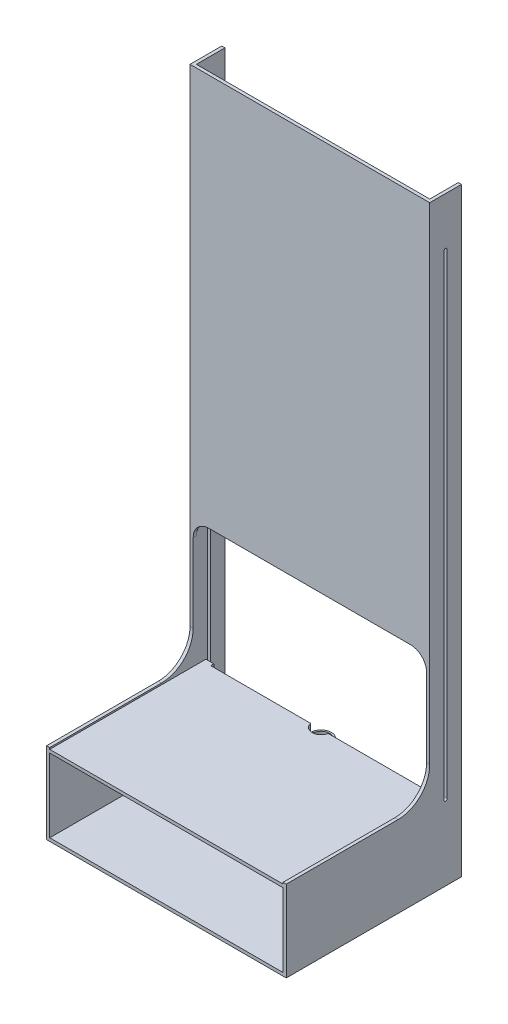
SolidWorks part; units mm, degrees
material "AISI 4340 Steel, annealed"
ref_plane "Front Plane" through (0, 0, 0) normal (0, 0, 1) x (1, 0, 0)
ref_plane "Top Plane" through (0, 0, 0) normal (0, 1, 0) x (1, 0, 0)
ref_plane "Right Plane" through (0, 0, 0) normal (1, 0, 0) x (0, 0, -1)
ref_plane "Right side of elevator platform" through (368, 0, 0) normal (1, 0, 0) x (0, 0, -1)
sketch "Sketch2" plane through (368, 0, 0) normal (1, 0, 0) x (0, 0, -1)
  line L0 (50, 236.5) -> (50, 1736.5) construction
  line L1 (45, 236.5) -> (45, 1736.5)
  line L2 (55, 236.5) -> (55, 1736.5)
  line L4 (0, 0) -> (100, 0)
  line L5 (0, 0) -> (0, 1800)
  line L6 (0, 1800) -> (100, 1800)
  line L7 (100, 0) -> (100, 1800)
  arc A0 (45, 236.5) -> (55, 236.5) centre (50, 236.5) ccw
  arc A1 (55, 1736.5) -> (45, 1736.5) centre (50, 1736.5) ccw
  point P2 (50, 986.5)
  dimension "D6" = 5
  dimension "D1" = 1800
  dimension "D2" = 100
  dimension "D3" = 50
  dimension "D4" = 236.5
  dimension "D5" = 63.5
extrude "Right side guide" add sketch "Sketch2" along normal blind 10
sketch "Sketch3" plane through (368, 0, 0) normal (-1, 0, 0) x (0, 0, 1)
  line L0 (0, 1800) -> (0, 0) construction
  line L1 (-100, 0) -> (0, 0)
  line L2 (-100, 0) -> (-100, 10)
  line L3 (-100, 10) -> (0, 10)
  line L4 (0, 0) -> (0, 10)
  dimension "D1" = 10
extrude "Bottom connection" add sketch "Sketch3" along normal blind 736
sketch "Sketch4" plane through (-368, 0, 0) normal (-1, 0, 0) x (0, 0, 1)
  line L0 (-55, 236.5) -> (-55, 1736.5) construction
  line L1 (-45, 1736.5) -> (-45, 236.5) construction
  line L2 (-55, 236.5) -> (-55, 1736.5)
  line L3 (-45, 1736.5) -> (-45, 236.5)
  line L4 (-100, 10) -> (0, 10)
  line L5 (0, 10) -> (0, 1800)
  line L6 (0, 1800) -> (-100, 1800)
  line L7 (-100, 1800) -> (-100, 10)
  line L9 (0, 10) -> (0, 1800)
  line L10 (0, 1800) -> (-100, 1800)
  line L11 (-100, 1800) -> (-100, 10)
  line L16 (-100, 10) -> (-100, 0)
  line L17 (-100, 0) -> (0, 0)
  line L18 (0, 0) -> (0, 10)
  line L19 (0, 10) -> (-100, 10)
  line L20 (-100, 10) -> (-100, 0)
  line L21 (-100, 0) -> (0, 0)
  line L22 (0, 0) -> (0, 10)
  arc A0 (-45, 1736.5) -> (-55, 1736.5) centre (-50, 1736.5) ccw construction
  arc A1 (-55, 236.5) -> (-45, 236.5) centre (-50, 236.5) ccw construction
  arc A2 (-45, 1736.5) -> (-55, 1736.5) centre (-50, 1736.5) ccw
  arc A3 (-55, 236.5) -> (-45, 236.5) centre (-50, 236.5) ccw
  dimension "D1" = 0
  dimension "D2" = 0
extrude "Left side guide" add sketch "Sketch4" along normal blind 10
sketch "Sketch5" plane through (0, 0, 0) normal (0, 0, 1) x (1, 0, 0)
  line L0 (-368, 10) -> (-368, 1800) construction
  line L1 (-368, 1800) -> (368, 1800)
  line L2 (-368, 1800) -> (-368, 653.8)
  line L3 (-368, 653.8) -> (368, 653.8)
  line L4 (368, 1800) -> (368, 653.8)
  line L5 (368, 1800) -> (368, 10) construction
  line L6 (378, 1800) -> (368, 1800) construction
  line L7 (-368, 10) -> (368, 10) construction
  dimension "D1" = 643.8
extrude "Structural webbing extrude" add sketch "Sketch5" against normal blind 10
sketch "Sketch6" plane through (0, 0, 0) normal (0, 0, 1) x (1, 0, 0)
  line L0 (-378, 251.5) -> (-378, 0)
  line L1 (-378, 0) -> (-378, 1800) construction
  line L2 (-378, 0) -> (378, 0)
  line L3 (378, 0) -> (378, 251.5)
  line L4 (378, 1800) -> (378, 0) construction
  line L5 (378, 251.5) -> (368, 251.5)
  line L6 (368, 653.8) -> (368, 10) construction
  line L7 (368, 251.5) -> (368, 10)
  line L8 (368, 10) -> (-368, 10)
  line L9 (-368, 10) -> (-368, 251.5)
  line L10 (-368, 10) -> (-368, 653.8) construction
  line L11 (-368, 251.5) -> (-378, 251.5)
  dimension "D1" = 241.5
extrude "Input roller holder extrude" add sketch "Sketch6" along normal blind 452.52
sketch "Sketch7" plane through (368, 0, 0) normal (-1, 0, 0) x (0, 0, 1)
  line L0 (0, 653.8) -> (0, 251.5) construction
  line L1 (452.52, 251.5) -> (-40, 251.5)
  line L2 (452.52, 251.5) -> (452.52, 241.5)
  line L3 (452.52, 241.5) -> (-40, 241.5)
  line L4 (-40, 251.5) -> (-40, 241.5)
  dimension "D1" = 40
  dimension "D2" = 10
extrude "Input roller platform" add sketch "Sketch7" along normal up to next
sketch "Sketch8" plane through (0, 251.5, 0) normal (0, 1, 0) x (1, 0, 0)
  line L1 (-378, -452.52) -> (-368, -452.52)
  line L2 (-378, -452.52) -> (-378, 0)
  line L3 (-378, 0) -> (-368, 0)
  line L4 (-368, -452.52) -> (-368, 0)
  line L5 (368, 0) -> (378, 0)
  line L6 (368, 0) -> (368, -452.52)
  line L7 (368, -452.52) -> (378, -452.52)
  line L8 (378, 0) -> (378, -452.52)
extrude "Siding outline" add sketch "Sketch8" along normal blind 5
sketch "Sketch9" plane through (0, 1800, 0) normal (0, 1, 0) x (1, 0, 0)
  line L8 (368, 100) -> (368, 10)
  line L9 (368, 10) -> (-368, 10)
  line L10 (-368, 10) -> (-368, 100)
  line L11 (-368, 100) -> (-378, 100)
  line L12 (-378, 100) -> (-378, 0)
  line L13 (-378, 0) -> (378, 0)
  line L14 (378, 0) -> (378, 100)
  line L15 (378, 100) -> (368, 100)
  line L16 (368, 100) -> (368, 10)
  line L17 (368, 10) -> (-368, 10)
  line L18 (-368, 10) -> (-368, 100)
  line L19 (-368, 100) -> (-378, 100)
  line L20 (-378, 100) -> (-378, 0)
  line L21 (-378, 0) -> (378, 0)
  line L22 (378, 0) -> (378, 100)
  line L23 (378, 100) -> (368, 100)
  dimension "D1" = 0
extrude "Lip to prevent box from falling out" add sketch "Sketch9" along normal blind 91.5
fillet "Vertical section fillets" radius 100 2 edges at (373, 256.5, 0) (-373, 256.5, 0)
fillet "Smaller fillets" radius 50 2 edges at (368, 653.8, -5) (-368, 653.8, -5)
sketch "Sketch11" plane through (0, 0, -40) normal (0, 0, -1) x (-1, 0, 0)
  line L0 (368, 251.5) -> (-368, 251.5) construction
  line L1 (-343, 251.5) -> (343, 251.5)
  line L2 (-343, 251.5) -> (-343, 241.5)
  line L3 (-343, 241.5) -> (343, 241.5)
  line L4 (343, 251.5) -> (343, 241.5)
  line L5 (368, 241.5) -> (-368, 241.5) construction
  line L6 (-368, 251.5) -> (-368, 241.5) construction
  line L7 (368, 251.5) -> (368, 241.5) construction
  dimension "D1" = 25
  dimension "D2" = 25
extrude "Gate spacing cut" cut sketch "Sketch11" against normal blind 10
sketch "Sketch12" plane through (-368, 0, 0) normal (1, 0, 0) x (0, 0, -1)
  line L1 (45, 221.5) -> (40, 221.5)
  line L2 (45, 221.5) -> (45, 10)
  line L3 (45, 10) -> (40, 10)
  line L4 (40, 221.5) -> (40, 10)
  line L5 (100, 1891.5) -> (100, 10) construction
  line L6 (45, 236.5) -> (45, 1736.5) construction
  line L7 (-452.52, 10) -> (100, 10) construction
  line L8 (40, 241.5) -> (-452.52, 241.5) construction
  line L9 (30, 241.5) -> (25, 241.5)
  line L10 (30, 241.5) -> (30, 10)
  line L11 (30, 10) -> (25, 10)
  line L12 (25, 241.5) -> (25, 10)
  dimension "D1" = 60
  dimension "D2" = 20
  dimension "D3" = 5
extrude "Gate guide rails" add sketch "Sketch12" along normal up to next
sketch "Sketch13" plane through (0, 0, -45) normal (0, 0, -1) x (-1, 0, 0)
  line L0 (-368, 221.5) -> (368, 221.5) construction
  line L1 (-328, 221.5) -> (328, 221.5)
  line L2 (-328, 221.5) -> (-328, 10)
  line L3 (-328, 10) -> (328, 10)
  line L4 (328, 221.5) -> (328, 10)
  line L5 (368, 10) -> (-368, 10) construction
  line L6 (-368, 10) -> (-368, 1891.5) construction
  point P8 (0, 221.5)
  dimension "D1" = 40
extrude "Gate rod connection cutout" cut sketch "Sketch13" against normal through all
sketch "Sketch14" plane through (0, 10, 0) normal (0, 1, 0) x (1, 0, 0)
  line L0 (328, 45) -> (-328, 25) construction
  circle A0 centre (0, 35) radius 28
  circle A1 centre (0, 35) radius 33
  point P7 (0, 35)
  dimension "D1" = 56
  dimension "D2" = 5
extrude "Spring cup" add sketch "Sketch14" along normal blind 75
sketch "Sketch15" plane through (0, 85, 0) normal (0, 1, 0) x (1, 0, 0)
  line L0 (368, 30) -> (328, 30) construction
  line L1 (32.619, 30) -> (27.55, 30)
  line L3 (32.619, 40) -> (27.55, 40)
  line L5 (-27.55, 40) -> (-32.619, 40)
  line L6 (-27.55, 30) -> (-32.619, 30)
  circle A0 centre (0, 35) radius 28 construction
  arc A1 (27.55, 40) -> (-27.55, 40) centre (0, 35) ccw
  circle A2 centre (0, 35) radius 33 construction
  arc A3 (32.619, 40) -> (-32.619, 40) centre (0, 35) ccw
  arc A4 (-27.55, 30) -> (27.55, 30) centre (0, 35) ccw
  arc A5 (-32.619, 30) -> (32.619, 30) centre (0, 35) ccw
extrude "Spring container extension" add sketch "Sketch15" along normal up to surface (136.5 mm away) up to face at (0, 221.5, -27.5)
sketch "Sketch16" plane through (0, 221.5, 0) normal (0, 1, 0) x (1, 0, 0)
  circle A0 centre (0, 35) radius 28
  arc A1 (27.55, 40) -> (-27.55, 40) centre (0, 35) ccw construction
extrude "Spring hole (can't insert spring without this)" cut sketch "Sketch16" along normal up to surface (30 mm away) up to face at (0, 251.5, 85.63)
sketch "Sketch17" plane through (0, 221.5, 0) normal (0, 1, 0) x (1, 0, 0)
  line L2 (-26.1534, 25) -> (-31.4484, 25)
  line L3 (31.4484, 25) -> (26.1534, 25)
  line L4 (-26.1534, 25) -> (-31.4484, 25)
  line L5 (31.4484, 25) -> (26.1534, 25)
  arc A2 (-31.4484, 25) -> (31.4484, 25) centre (0, 35) ccw
  arc A3 (-26.1534, 25) -> (26.1534, 25) centre (0, 35) ccw
  arc A4 (-31.4484, 25) -> (31.4484, 25) centre (0, 35) ccw
  arc A5 (-26.1534, 25) -> (26.1534, 25) centre (0, 35) ccw
  dimension "D1" = 0
extrude "Container extension to meet with conveyor plate" add sketch "Sketch17" along normal up to next
fillet "Spring holder fillets" radius 10 4 edges at (0, 10, -68) (-31.4484, 231.5, -25) (31.4484, 231.5, -25) (0, 241.5, -2)
